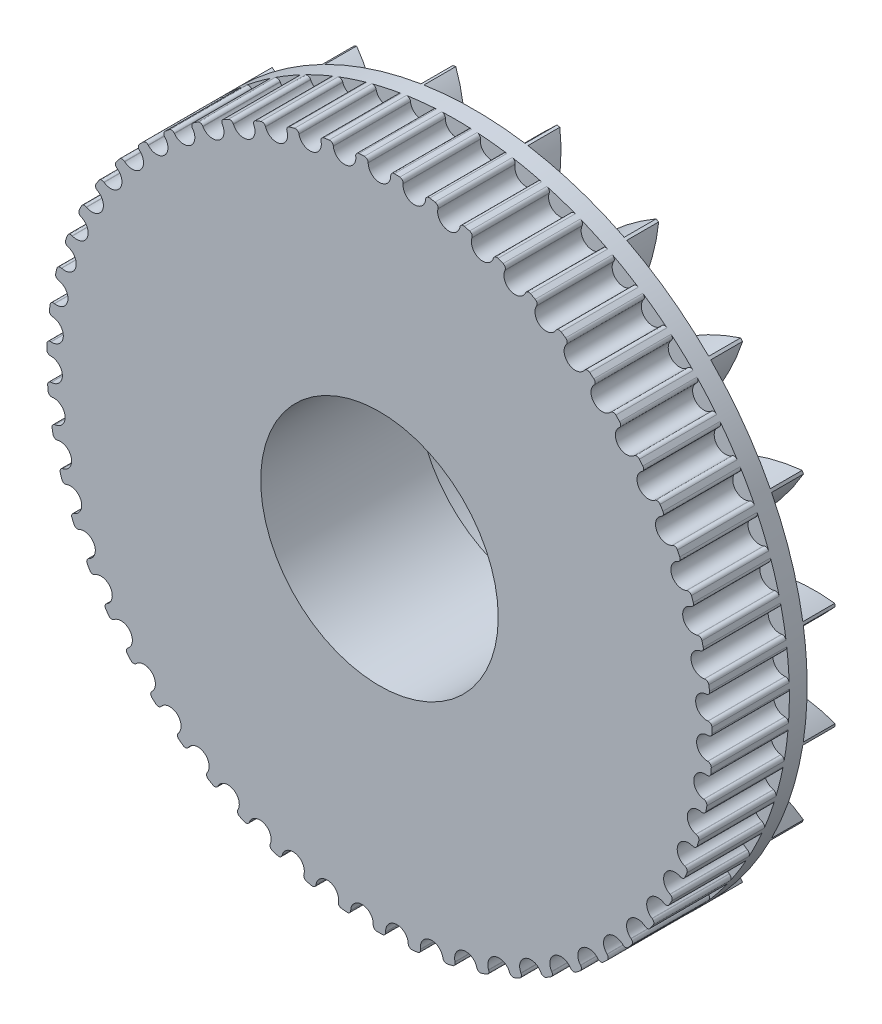
SolidWorks part; units mm, degrees
ref_plane "Ebene vorne" through (0, 0, 0) normal (0, 0, 1) x (1, 0, 0)
ref_plane "Ebene oben" through (0, 0, 0) normal (0, 1, 0) x (1, 0, 0)
ref_plane "Ebene rechts" through (0, 0, 0) normal (1, 0, 0) x (0, 0, -1)
ref_axis "Achse1" through (0, 0, 10.5) along (0, 0, -1)
sketch "Skizze1" plane through (0, 0, 0) normal (0, 1, 0) x (1, 0, 0)
  line L8 (-22.6426, 0) -> (-28.0075, 0)
  line L9 (-28.0075, 0) -> (-28.0075, 2.6824)
  line L20 (-22.6426, 0) -> (0, 0) construction
  line L21 (-28.0075, 2.6824) -> (-22.6426, 0)
  line L22 (-21.9953, 13.0928) -> (-28.0075, 2.6824) construction
  line L23 (-17.7821, 10.9861) -> (-21.9953, 13.0928) construction
  line L24 (0, 10.9861) -> (-17.7821, 10.9861) construction
  line L25 (0, 0) -> (0, 10.9861) construction
revolve "Rotation1" add sketch "Skizze1" angle 360 about L25
ref_plane "Ebene2" through (0, 4.5285, 9.0571) normal (0, 0.4472, 0.8944) x (1, 0, 0)
sketch "Skizze3" plane through (0, 4.5285, 9.0571) normal (0, 0.4472, 0.8944) x (1, 0, 0)
  arc A18 (-1.4236, 21.1116) -> (-4.8611, 26.4062) centre (-11.1009, 18.5919) ccw
  arc A19 (-1.4236, 21.1116) -> (-0.9483, 20.7597) centre (-0.9678, 21.2303) ccw
  arc A20 (0.9483, 20.7597) -> (-0.9483, 20.7597) centre (0, -2.1122) ccw
  arc A21 (0.9483, 20.7597) -> (1.4236, 21.1116) centre (0.9678, 21.2303) ccw
  arc A22 (4.8611, 26.4062) -> (1.4236, 21.1116) centre (11.1009, 18.5919) ccw
  arc A23 (4.8611, 26.4062) -> (-4.8611, 26.4062) centre (0, -2.1122) ccw
sketch "Skizze4" plane through (0, 0, 0) normal (1, 0, 0) x (0, 0, -1)
  line L1 (1.1824, 23.6426) -> (-4.8176, 23.6426)
  line L4 (2.6824, 28.0075) -> (2.6824, -28.0075) construction
  dimension "D1" = 1
  dimension "D2" = 6
  dimension "D3" = 1.5
sweep "Schnitt-Austragung1" cut profiles "Skizze3" path "Skizze4"
pattern_circular "Kreismuster1" count 20 over 360 of "Schnitt-Austragung1"
sketch "Skizze5" plane through (0, 0, 0) normal (0, 0, 1) x (1, 0, 0)
  circle A1 centre (0, 0) radius 28.0075
extrude "Aufsatz-Linear austragen1" add sketch "Skizze5" along normal blind 8
sketch "Skizze8" plane through (0, 0, 8) normal (0, 0, 1) x (1, 0, 0)
  line L0 (0, 0) -> (0, 28.0075) construction
  line L1 (-0.95, 27.6575) -> (-0.95, 27.9914)
  line L2 (0.95, 27.6575) -> (0.95, 27.9914)
  circle A3 centre (0, 0) radius 28.0075 construction
  arc A4 (-0.95, 27.6575) -> (0.95, 27.6575) centre (0, 27.6575) ccw
  arc A5 (0.95, 27.9914) -> (-0.95, 27.9914) centre (0, 0) ccw
  dimension "D1" = 1.9
  dimension "D2" = 1.3
extrude "Schnitt-Linear austragen3" cut sketch "Skizze8" against normal blind 6.5 contours A5 L1 A4 L2
fillet "Verrundung1" radius 0.3 2 edges at (0.95, 27.9914, 4.75) (-0.95, 27.9914, 4.75)
pattern_circular "Kreismuster4" count 59 over 360 about axis through (0, 0, 0) along (0, 0, 1) of "Schnitt-Linear austragen3", "Verrundung1"
sketch "Skizze9" plane through (0, 0, 8) normal (0, 0, 1) x (1, 0, 0)
  circle A0 centre (0, 0) radius 10
  dimension "D1" = 20
extrude "Schnitt-Linear austragen4" cut sketch "Skizze9" against normal through all
sketch "Skizze10" plane through (0, 0, 0) normal (0, 0, -1) x (-1, 0, 0)
  circle A0 centre (0, 0) radius 14
  circle A1 centre (0, 0) radius 13.5
  dimension "D1" = 28
  dimension "D2" = 27
extrude "Aufsatz-Linear austragen2" add sketch "Skizze10" along normal up to surface (9.3766 mm away)
sketch "Skizze11" plane through (0, 0, 0) normal (0, 0, -1) x (-1, 0, 0)
  circle A0 centre (0, 0) radius 10
  circle A1 centre (0, 0) radius 13.5 construction
  circle A2 centre (0, 0) radius 13.5
  dimension "D1" = 20
extrude "Aufsatz-Linear austragen4" add sketch "Skizze11" along normal offset from surface (5.1766 mm away) 4.2 up to face at (13.5, 0, -9.3766)
chamfer "Fase1" distance 0.5 angle 45 1 edges at (13.5, 0, -9.3766)
